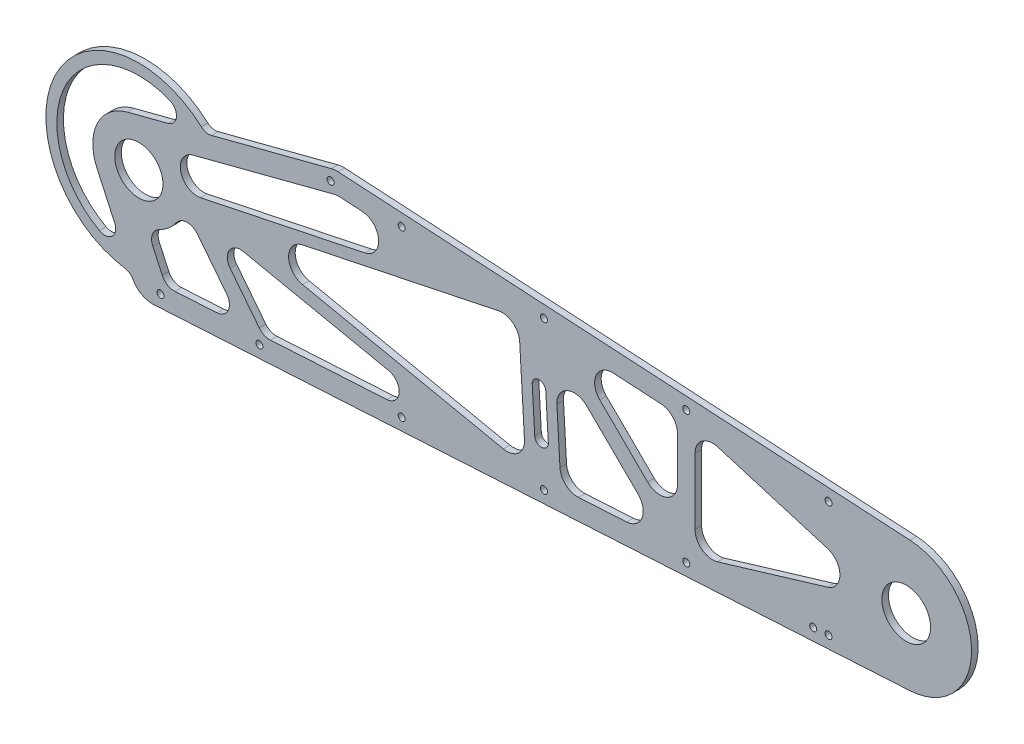
SolidWorks part; units mm, degrees
material "Thornel VCB-20 Carbon Cloth"
ref_plane "Front Plane" through (0, 0, 0) normal (0, 0, 1) x (1, 0, 0)
ref_plane "Top Plane" through (0, 0, 0) normal (0, 1, 0) x (1, 0, 0)
ref_plane "Right Plane" through (0, 0, 0) normal (1, 0, 0) x (0, 0, -1)
sketch "Sketch1" plane through (0, 0, 0) normal (0, 0, 1) x (1, 0, 0)
  line L0 (-175, 0) -> (175, 0) construction
  line L1 (-172.1122, 49.9165) -> (176.7203, 29.7354)
  line L2 (-172.1122, -49.9165) -> (176.7203, -29.7354)
  line L3 (139.566, 26.3757) -> (-120, 41.3925) construction
  line L4 (-55.1085, -37.6383) -> (9.783, -33.8841) construction
  line L5 (-125, 0) -> (-125, 62.9978) construction
  line L6 (-55.5713, 29.6383) -> (-120.4628, 33.3925) construction
  line L7 (-120.4628, 33.3925) -> (-120, 41.3925) construction
  line L8 (-55.5713, 29.6383) -> (-55.1085, 37.6383) construction
  line L9 (-88.0171, 31.5154) -> (-87.5543, 39.5154) construction
  line L10 (-120, -41.3925) -> (-165.1122, -44.0024) construction
  line L11 (139.566, -26.3757) -> (74.6745, -30.1299) construction
  circle A0 centre (175, 0) radius 11.1125
  arc A1 (176.7203, 29.7354) -> (176.7203, -29.7354) centre (175, 0) cw
  circle A3 centre (-175, 0) radius 22.5 construction
  circle A7 centre (-175, 0) radius 11
  circle A9 centre (-120, 41.3925) radius 1.6
  circle A10 centre (-55.1085, 37.6383) radius 1.6
  circle A11 centre (9.783, 33.8841) radius 1.6
  circle A12 centre (74.6745, 30.1299) radius 1.6
  circle A13 centre (139.566, 26.3757) radius 1.6
  circle A15 centre (139.566, -26.3757) radius 1.6
  circle A16 centre (74.6745, -30.1299) radius 1.6
  circle A17 centre (9.783, -33.8841) radius 1.6
  circle A18 centre (-55.1085, -37.6383) radius 1.6
  circle A19 centre (-120, -41.3925) radius 1.6
  arc A20 (-172.1122, 49.9165) -> (-172.1122, -49.9165) centre (-175, 0) ccw
  circle A21 centre (-87.5543, 39.5154) radius 1.6
  circle A22 centre (-165.1122, -44.0024) radius 1.6
  circle A23 centre (-165.1122, 44.0024) radius 1.6
  circle A24 centre (132.5777, -26.78) radius 1.6
  point P4 (0, 0)
  point P18 (-175, 22.5)
  point P21 (-197.5, 0)
  point P22 (-175, -22.5)
  point P23 (-152.5, 0)
  point P30 (-88.0171, 31.5154)
  dimension "D2" = 22.225
  dimension "D3" = 50
  dimension "D5" = 45
  dimension "D6" = 3.2
  dimension "D7" = 260
  dimension "D8" = 5
  dimension "D9" = 7
  dimension "D10" = 22
  dimension "D11" = 7
  dimension "D16" = 5
  dimension "D1" = 350
  dimension "D4" = 8
  dimension "D12" = 5.5
extrude "Boss-Extrude1" add sketch "Sketch1" along normal blind 3
sketch "Sketch4" plane through (0, 0, 3) normal (0, 0, 1) x (1, 0, 0)
  point P10 (-197.5, 0)
  point P13 (-175, 22.5)
  point P16 (-152.5, 0)
  point P19 (-175, -22.5)
hole_wizard "M3 Clearance Hole1" positions "Sketch4" profile "Sketch6" hole size "M3" standard "ANSI Metric" end condition up to next
sketch "Sketch6" plane through (-197.5, 0, 3) normal (1, 0, 0) x (0, -1, 0)
  line L0 (0, 0) -> (0, 3)
  line L1 (0, 3) -> (1.7, 3)
  line L2 (1.7, 3) -> (1.7, 0)
  line L5 (1.7, 0) -> (0, 0)
  line L11 (0, -6.35) -> (0, 107.95) construction
  dimension "Thru Hole Dia." = 3.4
  dimension "Thru Hole Depth" = 3
sketch "Sketch7" plane through (0, 0, 3) normal (0, 0, 1) x (1, 0, 0)
  line L0 (74.6745, 30.1299) -> (74.6745, -30.1299) construction
  line L1 (74.6745, -30.1299) -> (175, 0) construction
  line L2 (175, 0) -> (74.6745, 30.1299) construction
  line L3 (175, 0) -> (-152.5, 0) construction
  line L4 (175, -29.8349) -> (175, 29.8349) construction
  line L5 (88.9755, 22.7026) -> (139.0575, 7.6619)
  line L6 (139.0575, -7.6619) -> (88.9755, -22.7026)
  line L7 (78.6745, -15.0407) -> (78.6745, 15.0407)
  line L8 (9.783, -33.8841) -> (5.5294, 39.6394) construction
  line L9 (9.783, 33.8841) -> (74.6745, -30.1299) construction
  line L10 (9.783, 33.8841) -> (74.6745, 30.1299) construction
  line L11 (9.783, -33.8841) -> (74.6745, -30.1299) construction
  line L12 (-152.5, 0) -> (-55.1085, 37.6383) construction
  line L13 (-55.1085, 37.6383) -> (9.783, 33.8841) construction
  line L14 (9.783, 33.8841) -> (-152.5, 0) construction
  line L15 (70.6745, -1.436) -> (70.6745, 18.8041)
  line L16 (63.1365, 26.7907) -> (41.3408, 28.0517)
  line L17 (35.2605, 14.3698) -> (57.0563, -7.1312)
  line L18 (29.2743, 9.0376) -> (52.6422, -14.0143)
  line L19 (47.486, -27.6962) -> (25.5253, -28.9667)
  line L20 (17.0766, -21.4421) -> (15.6694, 2.8804)
  line L21 (176.7203, 29.7354) -> (-172.1122, 49.9165) construction
  line L22 (-172.1122, -49.9165) -> (176.7203, -29.7354) construction
  line L23 (0.8889, -18.6602) -> (-1.2973, 19.1278)
  line L24 (-10.9191, 26.4969) -> (-100.3161, 7.8311)
  line L25 (-100.3161, -7.8311) -> (-8.7329, -26.9534)
  line L35 (-197.5, 0) -> (-55.1085, 37.6383) construction
  line L52 (-55.1085, -37.6383) -> (-175, -22.5) construction
  line L53 (-15.2425, -47.7117) -> (-52.5586, -43) construction
  line L54 (-0.7058, -39.4678) -> (2.1851, -39.8329) construction
  line L55 (8.6627, -14.5198) -> (7.5076, 5.4468) construction
  line L56 (5.5679, -14.6989) -> (4.4127, 5.2678)
  line L57 (11.7575, -14.3408) -> (10.6024, 5.6258)
  line L58 (176.7203, 29.7354) -> (-172.1122, 49.9165) construction
  line L59 (-175, 22.5) -> (-165.1122, 44.0024) construction
  line L60 (-152.5, 0) -> (-120, 41.3925) construction
  line L61 (-133.3776, 17.8775) -> (-120.0806, 34.8127)
  line L62 (-115.0148, 37.0974) -> (-61.9156, 34.0254)
  line L63 (-61.0358, 22.1621) -> (-127.4321, 8.2988)
  line L64 (-168.6288, 26.7808) -> (-164.3288, 36.1317)
  line L65 (-158.531, 39.6149) -> (-139.3382, 38.5046)
  line L66 (-134.9656, 28.8093) -> (-148.2449, 11.8965)
  line L67 (-179.3293, 22.6595) -> (-175.2558, 31.5179)
  line L68 (-197.5, 0) -> (-225, 0) construction
  line L69 (-208.0189, 4) -> (-200.0799, 4)
  line L70 (-208.0189, -4) -> (-200.0799, -4)
  line L71 (-179.3293, -22.6595) -> (-175.2558, -31.5179)
  line L72 (-168.6288, -26.7808) -> (-164.3288, -36.1317)
  line L73 (-158.531, -39.6149) -> (-139.3382, -38.5046)
  line L74 (-134.9656, -28.8093) -> (-148.2449, -11.8965)
  line L75 (-115.0148, -37.0974) -> (-61.9156, -34.0254)
  line L76 (-133.3776, -17.8775) -> (-120.0806, -34.8127)
  line L77 (-61.0358, -22.1621) -> (-127.4321, -8.2988)
  arc A0 (139.0575, 7.6619) -> (139.0575, -7.6619) centre (136.7565, 0) cw
  arc A1 (88.9755, -22.7026) -> (78.6745, -15.0407) centre (86.6745, -15.0407) cw
  arc A2 (88.9755, 22.7026) -> (78.6745, 15.0407) centre (86.6745, 15.0407) ccw
  arc A3 (70.6745, 18.8041) -> (63.1365, 26.7907) centre (62.6745, 18.8041) ccw
  arc A4 (41.3408, 28.0517) -> (35.2605, 14.3698) centre (40.8787, 20.065) ccw
  arc A5 (70.6745, -1.436) -> (57.0563, -7.1312) centre (62.6745, -1.436) cw
  arc A6 (52.6422, -14.0143) -> (47.486, -27.6962) centre (47.024, -19.7095) cw
  arc A7 (25.5253, -28.9667) -> (17.0766, -21.4421) centre (25.0632, -20.98) cw
  arc A8 (29.2743, 9.0376) -> (15.6694, 2.8804) centre (23.6561, 3.3424) ccw
  arc A9 (0.8889, -18.6602) -> (-8.7329, -26.9534) centre (-7.0978, -19.1222) cw
  arc A10 (-1.2973, 19.1278) -> (-10.9191, 26.4969) centre (-9.2839, 18.6658) ccw
  arc A11 (-100.3161, 7.8311) -> (-100.3161, -7.8311) centre (-98.681, 0) ccw
  circle A30 centre (-175, 0) radius 11 construction
  circle A31 centre (-175, 0) radius 11 construction
  circle A32 centre (-175, 0) radius 22.5 construction
  circle A49 centre (9.783, -33.8841) radius 1.6 construction
  circle A50 centre (9.783, -33.8841) radius 1.6
  circle A52 centre (175, 0) radius 11.1125 construction
  circle A53 centre (175, 0) radius 11.1125 construction
  arc A56 (5.5679, -14.6989) -> (11.7575, -14.3408) centre (8.6627, -14.5198) ccw
  arc A57 (10.6024, 5.6258) -> (4.4127, 5.2678) centre (7.5076, 5.4468) ccw
  circle A58 centre (-165.1122, 44.0024) radius 1.6 construction
  circle A60 centre (-120, 41.3925) radius 1.6 construction
  arc A61 (-157.8609, 12.1348) -> (-165.8048, 18.8798) centre (-175, 0) ccw
  arc A62 (-182.6071, 19.5738) -> (-194.5066, 7.7778) centre (-175, 0) ccw
  arc A63 (-181.6995, 39.942) -> (-213.7614, 11.7391) centre (-175, 0) ccw
  arc A64 (-172.1122, 49.9165) -> (-172.1122, -49.9165) centre (-175, 0) ccw construction
  arc A65 (-175.2558, 31.5179) -> (-181.6995, 39.942) centre (-180.707, 34.0247) ccw
  arc A66 (-213.7614, 11.7391) -> (-208.0189, 4) centre (-208.0189, 10) ccw
  arc A67 (-194.5066, 7.7778) -> (-200.0799, 4) centre (-200.0799, 10) cw
  arc A68 (-182.6071, 19.5738) -> (-179.3293, 22.6595) centre (-184.7806, 25.1663) ccw
  arc A69 (-61.9156, 34.0254) -> (-61.0358, 22.1621) centre (-62.2621, 28.0354) cw
  arc A70 (-120.0806, 34.8127) -> (-115.0148, 37.0974) centre (-115.3614, 31.1074) cw
  arc A71 (-133.3776, 17.8775) -> (-127.4321, 8.2988) centre (-128.6584, 14.1721) ccw
  arc A72 (-139.3382, 38.5046) -> (-134.9656, 28.8093) centre (-139.6847, 32.5146) cw
  arc A73 (-164.3288, 36.1317) -> (-158.531, 39.6149) centre (-158.8776, 33.625) cw
  arc A74 (-165.8048, 18.8798) -> (-168.6288, 26.7808) centre (-163.1776, 24.2741) cw
  arc A75 (-157.8609, 12.1348) -> (-148.2449, 11.8965) centre (-152.9641, 15.6018) ccw
  arc A76 (-213.7614, -11.7391) -> (-208.0189, -4) centre (-208.0189, -10) cw
  arc A77 (-194.5066, -7.7778) -> (-200.0799, -4) centre (-200.0799, -10) ccw
  arc A78 (-182.6071, -19.5738) -> (-194.5066, -7.7778) centre (-175, 0) cw
  arc A79 (-181.6995, -39.942) -> (-213.7614, -11.7391) centre (-175, 0) cw
  arc A80 (-182.6071, -19.5738) -> (-179.3293, -22.6595) centre (-184.7806, -25.1663) cw
  arc A81 (-175.2558, -31.5179) -> (-181.6995, -39.942) centre (-180.707, -34.0247) cw
  arc A82 (-164.3288, -36.1317) -> (-158.531, -39.6149) centre (-158.8776, -33.625) ccw
  arc A83 (-165.8048, -18.8798) -> (-168.6288, -26.7808) centre (-163.1776, -24.2741) ccw
  arc A84 (-157.8609, -12.1348) -> (-165.8048, -18.8798) centre (-175, 0) cw
  arc A85 (-157.8609, -12.1348) -> (-148.2449, -11.8965) centre (-152.9641, -15.6018) cw
  arc A86 (-139.3382, -38.5046) -> (-134.9656, -28.8093) centre (-139.6847, -32.5146) ccw
  arc A87 (-61.9156, -34.0254) -> (-61.0358, -22.1621) centre (-62.2621, -28.0354) ccw
  arc A88 (-120.0806, -34.8127) -> (-115.0148, -37.0974) centre (-115.3614, -31.1074) ccw
  arc A89 (-133.3776, -17.8775) -> (-127.4321, -8.2988) centre (-128.6584, -14.1721) cw
  point P36 (164.5699, 0)
  point P59 (-137.8221, 0)
  point P102 (-15.2425, -47.7117)
  point P126 (8.0851, -4.5365)
  dimension "D8" = 8
  dimension "D11" = 10
  dimension "D12" = 5
  dimension "D20" = 3.1
  dimension "D10" = 4
  dimension "D17" = 6
  dimension "D1" = 3
  dimension "D3" = 8
  dimension "D4" = 8
  dimension "D5" = 8
  dimension "D6" = 16
  dimension "D7" = 6
  dimension "D9" = 8
  dimension "D13" = 8
  dimension "D14" = 5
  dimension "D15" = 8
  dimension "D16" = 24.8967
  dimension "D22" = 20
extrude "Cut-Extrude1" cut sketch "Sketch7" against normal blind 10 contours L57 A57 L56 A56 | L24 A11 L25 A9 L23 A10 | L18 A8 L20 A7 L19 A6 | A89 L76 A88 L75 A87 L77 | L20 A8 L18 A6 L19 A7 | L17 A5 L15 A3 L16 A4 | L7 A2 L5 A0 L6 A1 | L75 A87 L77 A89 L76 A88 | A82 L73 A86 L74 A85 A84 A83 L72 region at (32.1755, -11.823, 3) region at (-42.4165, -0.2065, 3) region at (8.0851, -4.5365, 3) region at (-98.5963, -24.3683, 3)
sketch "Sketch9" [suppressed] plane through (0, 0, 3) normal (0, 0, 1) x (1, 0, 0)
  line L2 (176.7203, 29.7354) -> (-172.1122, 49.9165) construction
  line L3 (-172.1122, -49.9165) -> (176.7203, -29.7354) construction
  line L4 (254.5375, 0) -> (208, 0) construction
  line L5 (200.557, 2) -> (203.931, 2)
  line L6 (200.557, -2) -> (203.931, -2)
  line L7 (162.9445, 26.3755) -> (155.7345, 26.7926)
  line L8 (162.9445, -26.3755) -> (155.7345, -26.7926)
  arc A1 (155.7345, -26.7926) -> (155.7345, 26.7926) centre (175, 0) ccw
  arc A2 (176.7203, -29.7354) -> (176.7203, 29.7354) centre (175, 0) ccw construction
  arc A3 (200.557, -2) -> (200.557, 2) centre (175, 0) ccw
  arc A4 (162.9445, 26.3755) -> (203.931, 2) centre (175, 0) cw
  arc A5 (203.931, -2) -> (162.9445, -26.3755) centre (175, 0) cw
  dimension "D1" = 33
  dimension "D2" = 4
  dimension "D3" = 4
extrude "Boss-Extrude2" [suppressed] add sketch "Sketch9" against normal up to surface (3 mm away)
fillet "Fillet1" [suppressed] radius 1
fillet "Fillet2" [suppressed] radius 80
sketch "Sketch10" plane through (0, 0, 3) normal (0, 0, 1) x (1, 0, 0)
  line L0 (-165.1122, 44.0024) -> (-120, 41.3925) construction
  line L1 (-165.1122, 44.0024) -> (-210.2243, 46.6123) construction
  line L2 (-172.1122, 49.9165) -> (-210.905, 52.1608)
  line L3 (176.7203, 29.7354) -> (-172.1122, 49.9165) construction
  line L4 (-216.1854, 47.458) -> (-217.3977, 26.5035)
  line L5 (-172.1122, 49.9165) -> (-217.3977, 26.5035)
  circle A0 centre (-120, 41.3925) radius 1.6 construction
  circle A1 centre (-165.1122, 44.0024) radius 1.6 construction
  circle A2 centre (-210.2243, 46.6123) radius 1.6
  arc A3 (-172.1122, 49.9165) -> (-172.1122, -49.9165) centre (-175, 0) ccw construction
  arc A4 (-210.905, 52.1608) -> (-216.1854, 47.458) centre (-211.1938, 47.1692) ccw
  dimension "D2" = 5
  dimension "D1" = 6
extrude "Boss-Extrude3" [suppressed] add sketch "Sketch10" against normal up to surface (3 mm away)
mirror "Mirror1" [suppressed] about plane through (0, 0, 0) normal (0, 1, 0)
sketch "Sketch13" plane through (0, 0, 3) normal (0, 0, 1) x (1, 0, 0)
  circle A1 centre (-120, 41.3925) radius 1.6 construction
  circle A2 centre (-165.1122, 44.0024) radius 1.6 construction
  circle A3 centre (-152.5, 0) radius 1.7 construction
  circle A4 centre (-175, 22.5) radius 1.7 construction
  circle A5 centre (-197.5, 0) radius 1.7 construction
  circle A6 centre (-175, -22.5) radius 1.7 construction
  circle A8 centre (-120, 41.3925) radius 1.6
  circle A9 centre (-165.1122, 44.0024) radius 1.6
  circle A10 centre (-152.5, 0) radius 1.7
  circle A11 centre (-175, 22.5) radius 1.7
  circle A12 centre (-197.5, 0) radius 1.7
  circle A13 centre (-175, -22.5) radius 1.7
extrude "Boss-Extrude4" add sketch "Sketch13" against normal up to surface (3 mm away) up to face at (56.1489, 13.0862, 0)
sketch "Sketch12" plane through (0, 0, 0) normal (0, 0, 1) x (1, 0, 0)
  line L0 (176.7203, 29.7354) -> (-172.1122, 49.9165) construction
  line L1 (-180.2821, 20.3249) -> (-85.6614, 44.9151)
  line L2 (176.7203, 29.7354) -> (-172.1122, 49.9165) construction
  line L3 (-175.1216, -49.9999) -> (-194.0794, -8.7736)
  line L4 (-168.6288, -26.7808) -> (-164.3288, -36.1317) construction
  line L5 (-172.1122, 49.9165) -> (-85.6614, 44.9151)
  line L6 (-150.3194, 18.2961) -> (-85.9362, 35.0281)
  line L7 (-146.7921, 3.2349) -> (-71.9712, 18.8573)
  line L9 (-10.9191, 26.4969) -> (-100.3161, 7.8311) construction
  line L10 (-83.4619, 35.2719) -> (-73.1442, 34.675)
  line L11 (63.1365, 26.7907) -> (41.3408, 28.0517) construction
  line L12 (-191.9615, 12.3818) -> (-87.5543, 39.5154) construction
  arc A0 (-194.0794, -8.7736) -> (-180.2821, 20.3249) centre (-175, 0) cw
  arc A1 (-71.9712, 18.8573) -> (-73.1442, 34.675) centre (-73.6063, 26.6884) ccw
  arc A2 (-85.9362, 35.0281) -> (-83.4619, 35.2719) centre (-83.924, 27.2853) cw
  arc A3 (-172.1122, 49.9165) -> (-172.1122, -49.9165) centre (-175, 0) ccw construction
  circle A4 centre (-175, 0) radius 11 construction
  arc A6 (-175.1216, -49.9999) -> (-172.1122, 49.9165) centre (-175, 0) cw
  arc A7 (-172.1122, 49.9165) -> (-172.1122, -49.9165) centre (-175, 0) ccw construction
  circle A13 centre (-87.5543, 39.5154) radius 1.6 construction
  arc A14 (-150.3194, 18.2961) -> (-146.7921, 3.2349) centre (-148.3734, 10.8082) ccw
  arc A15 (-157.8609, -12.1348) -> (-180.2821, 20.3249) centre (-175, 0) ccw construction
  dimension "D1" = 10
  dimension "D5" = 8
  dimension "D3" = 9.5
  dimension "D4" = 5
extrude "Cut-Extrude2" cut sketch "Sketch12" against normal through all both and the other way through all
fillet "Fillet3" radius 10 2 edges at (-85.6614, 44.9151, 1.5) (-175.1216, -49.9999, 1.5)
sketch "Sketch14" plane through (0, 0, 0) normal (0, 0, -1) x (-1, 0, 0)
  line L0 (177.9317, -43.8888) -> (194.0794, -8.7736) construction
  line L1 (180.2821, 20.3249) -> (87.1839, 44.5194) construction
  line L2 (181.1497, -36.8909) -> (178.6903, -42.2391)
  line L3 (150.3293, 28.109) -> (144.6321, 29.5897)
  arc A0 (181.1497, -36.8909) -> (150.3293, 28.109) centre (175, 0) ccw
  arc A1 (178.6903, -42.2391) -> (144.6321, 29.5897) centre (175, 0) ccw
  circle A2 centre (175, 0) radius 11 construction
  circle A3 centre (175, 0) radius 11 construction
  dimension "D1" = 42.4
  dimension "D2" = 5
extrude "Boss-Extrude5" add sketch "Sketch14" against normal up to surface (3 mm away) up to face at (-64.7542, 1.1454, 3)
fillet "Fillet4" radius 5 4 edges at (-178.6903, -42.2391, 1.5) (-181.1497, -36.8909, 1.5) (-144.6321, 29.5897, 1.5) (-150.3293, 28.109, 1.5)
